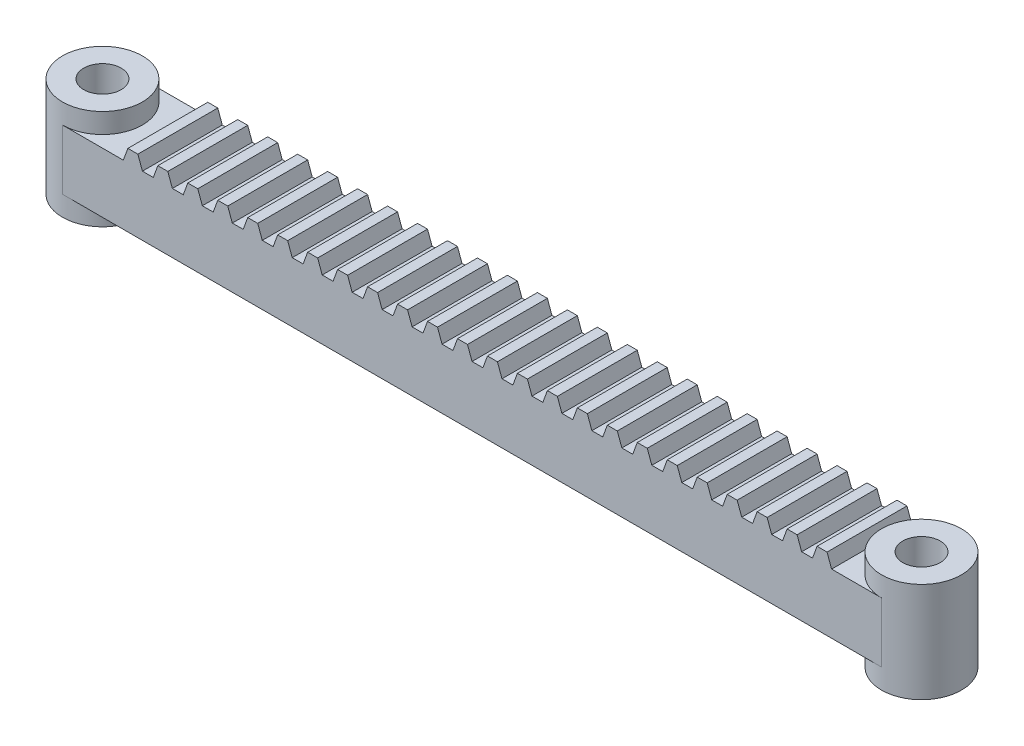
SolidWorks part; units mm, degrees
material "Galvanized Steel"
ref_plane "Front Plane" through (0, 0, 0) normal (0, 0, 1) x (1, 0, 0)
ref_plane "Top Plane" through (0, 0, 0) normal (0, 1, 0) x (1, 0, 0)
ref_plane "Right Plane" through (0, 0, 0) normal (1, 0, 0) x (0, 0, -1)
sketch "Sketch2" plane through (0, 0, 0) normal (0, 1, 0) x (1, 0, 0)
  line L0 (-82, 0) -> (82, 0) construction
  line L1 (-82, 8) -> (82, 8)
  line L2 (-82, -8) -> (82, -8)
  arc A0 (-82, 8) -> (-82, -8) centre (-82, 0) ccw
  arc A1 (82, -8) -> (82, 8) centre (82, 0) ccw
  circle A2 centre (-82, 0) radius 3.75
  circle A3 centre (82, 0) radius 3.75
  circle A4 centre (-82, 0) radius 8
  circle A5 centre (82, 0) radius 8
  point P2 (0, 0)
  dimension "D3" = 7.5
  dimension "D1" = 16
  dimension "D2" = 164
extrude "Boss-Extrude1" add sketch "Sketch2" along normal blind 12 contours L0 A4 L2 A5 | A4 L0 A5 L1 | A1 A5 A3 | A2 A4 A0 region at (-76.5031, 0, 5.4969) region at (0, 0, -4.0502) region at (0, 0, 4.0502) region at (76.5031, 0, -5.4969)
sketch "Sketch3" plane through (0, 0, 0) normal (0, 0, 1) x (1, 0, 0)
  line L0 (70.0901, 12) -> (70.0901, 14.5) construction
  line L2 (69.0901, 14.5) -> (71.0901, 14.5)
  line L3 (71.0901, 14.5) -> (72, 12)
  line L4 (72, 12) -> (68.1801, 12)
  line L5 (69.0901, 14.5) -> (68.1801, 12)
  line L6 (90, 0) -> (90, 12) construction
  line L7 (66, 12) -> (62.1801, 12)
  line L8 (63.0901, 14.5) -> (62.1801, 12)
  line L9 (63.0901, 14.5) -> (65.0901, 14.5)
  line L10 (65.0901, 14.5) -> (66, 12)
  line L11 (60, 12) -> (56.1801, 12)
  line L12 (57.0901, 14.5) -> (56.1801, 12)
  line L13 (57.0901, 14.5) -> (59.0901, 14.5)
  line L14 (59.0901, 14.5) -> (60, 12)
  line L15 (54, 12) -> (50.1801, 12)
  line L16 (51.0901, 14.5) -> (50.1801, 12)
  line L17 (51.0901, 14.5) -> (53.0901, 14.5)
  line L18 (53.0901, 14.5) -> (54, 12)
  line L19 (48, 12) -> (44.1801, 12)
  line L20 (45.0901, 14.5) -> (44.1801, 12)
  line L21 (45.0901, 14.5) -> (47.0901, 14.5)
  line L22 (47.0901, 14.5) -> (48, 12)
  line L23 (42, 12) -> (38.1801, 12)
  line L24 (39.0901, 14.5) -> (38.1801, 12)
  line L25 (39.0901, 14.5) -> (41.0901, 14.5)
  line L26 (41.0901, 14.5) -> (42, 12)
  line L27 (36, 12) -> (32.1801, 12)
  line L28 (33.0901, 14.5) -> (32.1801, 12)
  line L29 (33.0901, 14.5) -> (35.0901, 14.5)
  line L30 (35.0901, 14.5) -> (36, 12)
  line L31 (30, 12) -> (26.1801, 12)
  line L32 (27.0901, 14.5) -> (26.1801, 12)
  line L33 (27.0901, 14.5) -> (29.0901, 14.5)
  line L34 (29.0901, 14.5) -> (30, 12)
  line L35 (24, 12) -> (20.1801, 12)
  line L36 (21.0901, 14.5) -> (20.1801, 12)
  line L37 (21.0901, 14.5) -> (23.0901, 14.5)
  line L38 (23.0901, 14.5) -> (24, 12)
  line L39 (18, 12) -> (14.1801, 12)
  line L40 (15.0901, 14.5) -> (14.1801, 12)
  line L41 (15.0901, 14.5) -> (17.0901, 14.5)
  line L42 (17.0901, 14.5) -> (18, 12)
  line L43 (12, 12) -> (8.1801, 12)
  line L44 (9.0901, 14.5) -> (8.1801, 12)
  line L45 (9.0901, 14.5) -> (11.0901, 14.5)
  line L46 (11.0901, 14.5) -> (12, 12)
  line L47 (6, 12) -> (2.1801, 12)
  line L48 (3.0901, 14.5) -> (2.1801, 12)
  line L49 (3.0901, 14.5) -> (5.0901, 14.5)
  line L50 (5.0901, 14.5) -> (6, 12)
  line L51 (0, 12) -> (-3.8199, 12)
  line L52 (-2.9099, 14.5) -> (-3.8199, 12)
  line L53 (-2.9099, 14.5) -> (-0.9099, 14.5)
  line L54 (-0.9099, 14.5) -> (0, 12)
  line L55 (-6, 12) -> (-9.8199, 12)
  line L56 (-8.9099, 14.5) -> (-9.8199, 12)
  line L57 (-8.9099, 14.5) -> (-6.9099, 14.5)
  line L58 (-6.9099, 14.5) -> (-6, 12)
  line L59 (-12, 12) -> (-15.8199, 12)
  line L60 (-14.9099, 14.5) -> (-15.8199, 12)
  line L61 (-14.9099, 14.5) -> (-12.9099, 14.5)
  line L62 (-12.9099, 14.5) -> (-12, 12)
  line L63 (-18, 12) -> (-21.8199, 12)
  line L64 (-20.9099, 14.5) -> (-21.8199, 12)
  line L65 (-20.9099, 14.5) -> (-18.9099, 14.5)
  line L66 (-18.9099, 14.5) -> (-18, 12)
  line L67 (-24, 12) -> (-27.8199, 12)
  line L68 (-26.9099, 14.5) -> (-27.8199, 12)
  line L69 (-26.9099, 14.5) -> (-24.9099, 14.5)
  line L70 (-24.9099, 14.5) -> (-24, 12)
  line L71 (-30, 12) -> (-33.8199, 12)
  line L72 (-32.9099, 14.5) -> (-33.8199, 12)
  line L73 (-32.9099, 14.5) -> (-30.9099, 14.5)
  line L74 (-30.9099, 14.5) -> (-30, 12)
  line L75 (-36, 12) -> (-39.8199, 12)
  line L76 (-38.9099, 14.5) -> (-39.8199, 12)
  line L77 (-38.9099, 14.5) -> (-36.9099, 14.5)
  line L78 (-36.9099, 14.5) -> (-36, 12)
  line L79 (-42, 12) -> (-45.8199, 12)
  line L80 (-44.9099, 14.5) -> (-45.8199, 12)
  line L81 (-44.9099, 14.5) -> (-42.9099, 14.5)
  line L82 (-42.9099, 14.5) -> (-42, 12)
  line L83 (-48, 12) -> (-51.8199, 12)
  line L84 (-50.9099, 14.5) -> (-51.8199, 12)
  line L85 (-50.9099, 14.5) -> (-48.9099, 14.5)
  line L86 (-48.9099, 14.5) -> (-48, 12)
  line L95 (-82, 12) -> (82, 12) construction
  line L96 (-54, 12) -> (-57.8199, 12)
  line L97 (-56.9099, 14.5) -> (-57.8199, 12)
  line L98 (-56.9099, 14.5) -> (-54.9099, 14.5)
  line L99 (-54.9099, 14.5) -> (-54, 12)
  line L100 (-60, 12) -> (-63.8199, 12)
  line L101 (-62.9099, 14.5) -> (-63.8199, 12)
  line L102 (-62.9099, 14.5) -> (-60.9099, 14.5)
  line L103 (-60.9099, 14.5) -> (-60, 12)
  line L104 (-66, 12) -> (-69.8199, 12)
  line L105 (-68.9099, 14.5) -> (-69.8199, 12)
  line L106 (-68.9099, 14.5) -> (-66.9099, 14.5)
  line L107 (-66.9099, 14.5) -> (-66, 12)
  dimension "D1" = 40
  dimension "D2" = 2
  dimension "D4" = 18
  dimension "D6" = 6
  dimension "D3" = 2.5
  dimension "D5" = 24
extrude "Boss-Extrude2" add sketch "Sketch3" against normal up to surface (8 mm away) from surface up to face at (0, 6, -8) starting at face at (0, 6, 8)
extrude "Boss-Extrude3" add sketch "Sketch2<3>" along normal offset from surface 4 and the other way offset from surface 4 contours A1 A5 A3 | A2 A4 A0 region at (-76.5031, 0, -5.4969) region at (87.4969, 0, -5.4969) up to face at (-64.9099, 12, 0) offset beyond the face yes other way up to face at (0, 0, 0)
sketch "Sketch2<3>" plane through (0, 0, 0) normal (0, 1, 0) x (1, 0, 0) same geometry as "Sketch2"
equation "\"B\"= 24"
equation "\"D5@Sketch3\"=\"B\""
equation "\"C\"= 4"
equation "\"D1@Boss-Extrude3\"=\"C\""
equation "\"D2@Boss-Extrude3\"=\"C\""
equation "\"A\"= 164"
equation "\"D2@Sketch2\"=\"A\""
